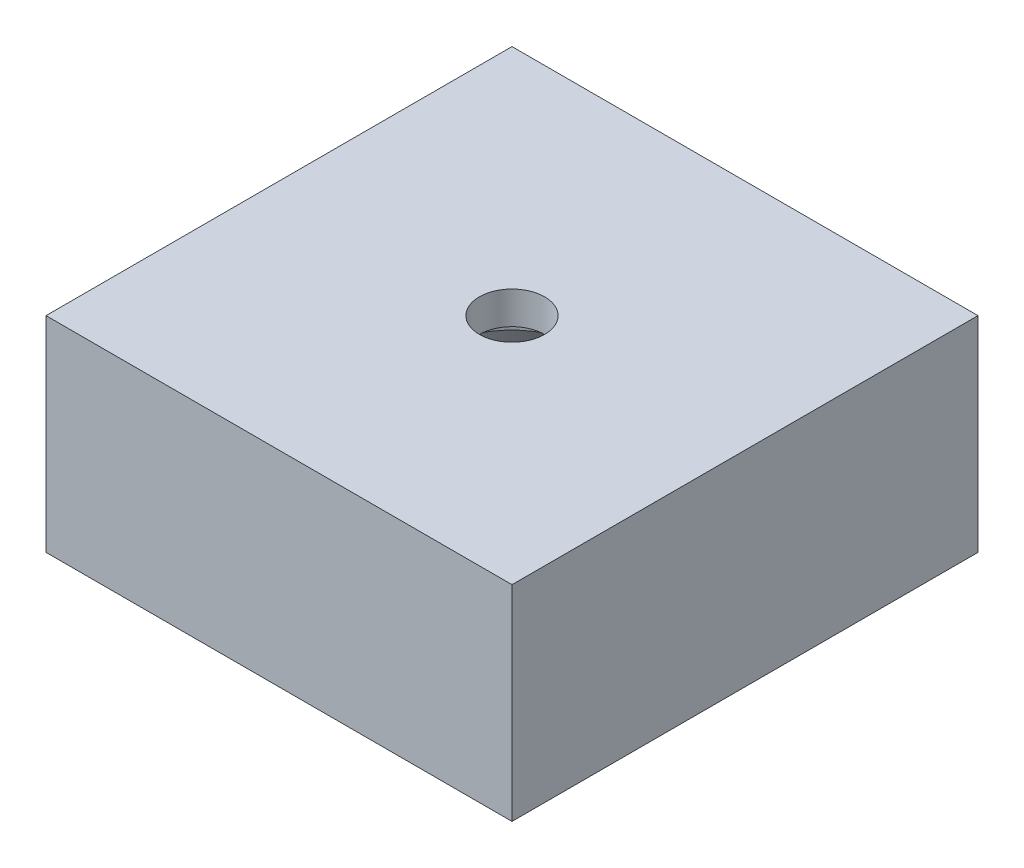
SolidWorks part; units mm, degrees
ref_plane "Front Plane" through (0, 0, 0) normal (0, 0, 1) x (1, 0, 0)
ref_plane "Top Plane" through (0, 0, 0) normal (0, 1, 0) x (1, 0, 0)
ref_plane "Right Plane" through (0, 0, 0) normal (1, 0, 0) x (0, 0, -1)
sketch "Sketch1" plane through (0, 0, 0) normal (0, 1, 0) x (1, 0, 0)
  line L0 (-25, 25) -> (25, -25) construction
  line L1 (-25, 25) -> (25, 25)
  line L2 (-25, 25) -> (-25, -25)
  line L3 (-25, -25) -> (25, -25)
  line L4 (25, 25) -> (25, -25)
  point P4 (0, 0)
  point P8 (0, 0)
  dimension "D1" = 50
extrude "Boss-Extrude1" add sketch "Sketch1" along normal blind 11 and the other way blind 11
sketch "Sketch2" plane through (0, 0, 0) normal (0, 0, 1) x (1, 0, 0)
  line L0 (-25, -11) -> (25, -11) construction
  line L1 (-3.5, 7.5) -> (-3.5, 11)
  line L2 (-3.5, 11) -> (0, 11)
  line L3 (-25, 11) -> (25, 11) construction
  line L5 (-18, -11) -> (-10.5, 4)
  line L6 (-10.5, 4) -> (-8, 4)
  line L7 (-8, 4) -> (-8, 7.5)
  line L8 (-8, 7.5) -> (-3.5, 7.5)
  line L9 (0, 11) -> (0, -11)
  line L10 (0, -11) -> (-18, -11)
  line L11 (-8, 4) -> (-8, -11) construction
  line L12 (-10.5, 4) -> (-10.5, -11) construction
  point P4 (-3.2947, 11)
  point P12 (0, 0)
  dimension "D1" = 8
  dimension "D2" = 18
  dimension "D3" = 3.5
  dimension "D4" = 2.5
  dimension "D5" = 3.5
  dimension "D6" = 3.5
revolve "Cut-Revolve1" cut sketch "Sketch2" angle 360 about L9
